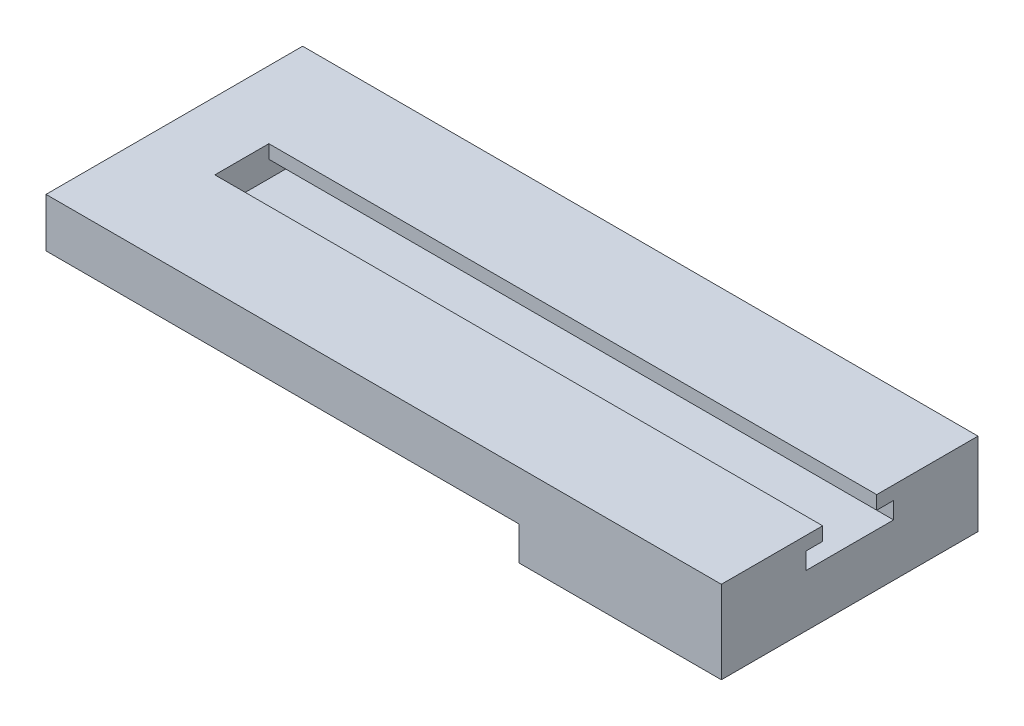
SolidWorks part; units mm, degrees
ref_plane "Front Plane" through (0, 0, 0) normal (0, 0, 1) x (1, 0, 0)
ref_plane "Top Plane" through (0, 0, 0) normal (0, 1, 0) x (1, 0, 0)
ref_plane "Right Plane" through (0, 0, 0) normal (1, 0, 0) x (0, 0, -1)
sketch "Sketch1" plane through (0, 0, 0) normal (0, 1, 0) x (1, 0, 0)
  line L2 (20, -16) -> (200, -16)
  line L3 (200, -16) -> (200, -46)
  line L4 (200, -46) -> (0, -46)
  line L7 (200, 30) -> (200, 0)
  line L8 (20, -16) -> (20, 0)
  line L9 (20, 0) -> (200, 0)
  line L10 (200, 30) -> (0, 30)
  line L11 (0, 30) -> (0, -46)
  dimension "D1" = 16
  dimension "D2" = 30
  dimension "D3" = 30
  dimension "D4" = 200
  dimension "D5" = 180
  dimension "D6" = 200
extrude "Boss-Extrude1" add sketch "Sketch1" along normal blind 4
sketch "Sketch2" plane through (0, 0, 0) normal (0, 1, 0) x (1, 0, 0)
  line L0 (209.7303, -8) -> (-59.5425, -8) construction
  line L1 (200, -8) -> (200, 5) construction
  line L4 (200, 5) -> (200, 30)
  line L5 (200, 30) -> (0, 30)
  line L6 (0, 30) -> (0, -46)
  line L7 (0, 30) -> (0, -46) construction
  line L8 (200, -21) -> (200, -46)
  line L10 (200, -46) -> (0, -46)
  line L11 (200, 5) -> (20, 5)
  line L12 (20, 5) -> (20, -21)
  line L13 (20, -21) -> (200, -21)
  point P18 (0, -8)
  point P19 (0, -8)
  dimension "D1" = 13
extrude "Boss-Extrude2" add sketch "Sketch2" against normal blind 5
sketch "Sketch3" plane through (0, 0, 0) normal (0, 1, 0) x (1, 0, 0)
  line L0 (0, 30) -> (200, 30)
  line L1 (200, 30) -> (200, -46)
  line L2 (200, -46) -> (0, -46)
  line L3 (0, -46) -> (0, 30)
extrude "Boss-Extrude3" add sketch "Sketch3" against normal blind 5.5 from offset 5 offset against normal yes
sketch "Sketch4" plane through (0, 0, 0) normal (0, 1, 0) x (1, 0, 0)
  line L0 (200, 30) -> (200, -46)
  line L1 (200, -46) -> (140, -46)
  line L2 (0, -46) -> (200, -46) construction
  line L3 (140, -46) -> (140, 30)
  line L4 (200, 30) -> (0, 30) construction
  line L5 (140, 30) -> (200, 30)
  dimension "D1" = 60
extrude "Boss-Extrude4" add sketch "Sketch4" against normal blind 10 from offset 10.5 contours L5 L0 L1 L3 offset against normal yes
sketch "Sketch5" plane through (0, 0, 0) normal (0, 1, 0) x (1, 0, 0)
  line L0 (170, -46) -> (170, 30) construction
  line L1 (200, -46) -> (140, -46) construction
  line L2 (140, 30) -> (200, 30) construction
  line L3 (200, -8) -> (140, -8) construction
  line L4 (200, 30) -> (200, -46) construction
  line L5 (140, -46) -> (140, 30) construction
  circle A0 centre (170, -8) radius 10.5
  dimension "D1" = 21
extrude "Cut-Extrude1" cut sketch "Sketch5" along normal blind 4 from offset 20.5 offset against normal yes
